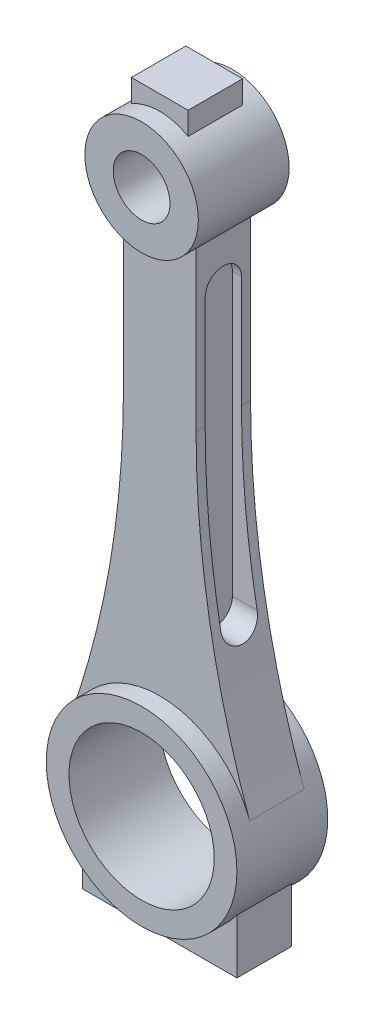
SolidWorks part; units mm, degrees
ref_plane "Front Plane" through (0, 0, 0) normal (0, 0, 1) x (1, 0, 0)
ref_plane "Top Plane" through (0, 0, 0) normal (0, 1, 0) x (1, 0, 0)
ref_plane "Right Plane" through (0, 0, 0) normal (1, 0, 0) x (0, 0, -1)
sketch "Sketch1" plane through (0, 0, 0) normal (0, 0, 1) x (1, 0, 0)
  line L0 (0, 135.8253) -> (0, -24.3288) construction
  line L1 (-8, 75.3953) -> (-8, 110.3953)
  line L2 (8, 75.3953) -> (8, 110.3953)
  line L3 (6.25, 135.8253) -> (-6.25, 135.8253)
  line L4 (-6.25, 135.8253) -> (-6.25, 130.8253)
  line L5 (6.25, 135.8253) -> (6.25, 130.8253)
  line L6 (-17, -24.3288) -> (-17, -12.3288)
  line L7 (-17, -24.3288) -> (17, -24.3288)
  line L8 (17, -24.3288) -> (17, -12.3288)
  circle A0 centre (0, 0) radius 21
  circle A1 centre (0, 0) radius 16
  circle A2 centre (0, 120) radius 12.5
  circle A3 centre (0, 120) radius 6.25
  arc A4 (-8, 75.3953) -> (-19.7874, 7.0327) centre (-212.1328, 75.3953) cw
  arc A5 (8, 75.3953) -> (19.7874, 7.0327) centre (212.1328, 75.3953) ccw
  dimension "D2" = 32
  dimension "D3" = 42
  dimension "D4" = 12.5
  dimension "D5" = 25
  dimension "D6" = 8
  dimension "D1" = 120
  dimension "D7" = 35
  dimension "D8" = 12.5
  dimension "D9" = 5
  dimension "D10" = 34
  dimension "D11" = 12
extrude "Boss-Extrude1" add sketch "Sketch1" along normal mid plane 20 contours A2 L0 A3 | L0 A2 A3 | A0 L0 A1 | L0 A0 A1 region at (3.1629, 131.8041, 0) region at (-0.2795, 129.375, 0) region at (11.8394, 16.7728, 0) region at (-0.4696, 18.5, 0)
extrude "Boss-Extrude2" add sketch "Sketch1<3>" along normal mid plane 12 contours A2 L0 A0 A5 L2 | L0 A2 L1 A4 A0 | A0 L0 L7 L8 | L3 L0 A2 L5 | L0 L3 L4 A2 | L0 A0 L6 L7 region at (3.3472, 133.8599, 0) region at (-3.3472, 133.8599, 0) region at (-5.3967, 57.8448, 0) region at (5.3967, 57.8448, 0) region at (-10.4494, -20.8498, 0) region at (10.4494, -20.8498, 0)
sketch "Sketch1<3>" plane through (0, 0, 0) normal (0, 0, 1) x (1, 0, 0) same geometry as "Sketch1"
sketch "Sketch2" plane through (0, 0, 0) normal (1, 0, 0) x (0, 0, -1)
  line L0 (0, 100) -> (0, 38) construction
  line L1 (4, 100) -> (4, 38)
  line L2 (-4, 100) -> (-4, 38)
  line L3 (-10, 120) -> (10, 120) construction
  line L4 (-10, 132.5) -> (-10, 107.5) construction
  line L5 (10, 107.5) -> (10, 132.5) construction
  arc A0 (4, 100) -> (-4, 100) centre (0, 100) ccw
  arc A1 (-4, 38) -> (4, 38) centre (0, 38) ccw
  point P3 (0, 69)
  dimension "D2" = 4
  dimension "D1" = 20
  dimension "D3" = 62
extrude "Cut-Extrude1" cut sketch "Sketch2" along normal through all from offset 6
extrude "Cut-Extrude3" cut sketch "Sketch2<3>" against normal through all from offset 6 offset against normal yes
sketch "Sketch2<3>" plane through (0, 0, 0) normal (1, 0, 0) x (0, 0, -1) same geometry as "Sketch2"
